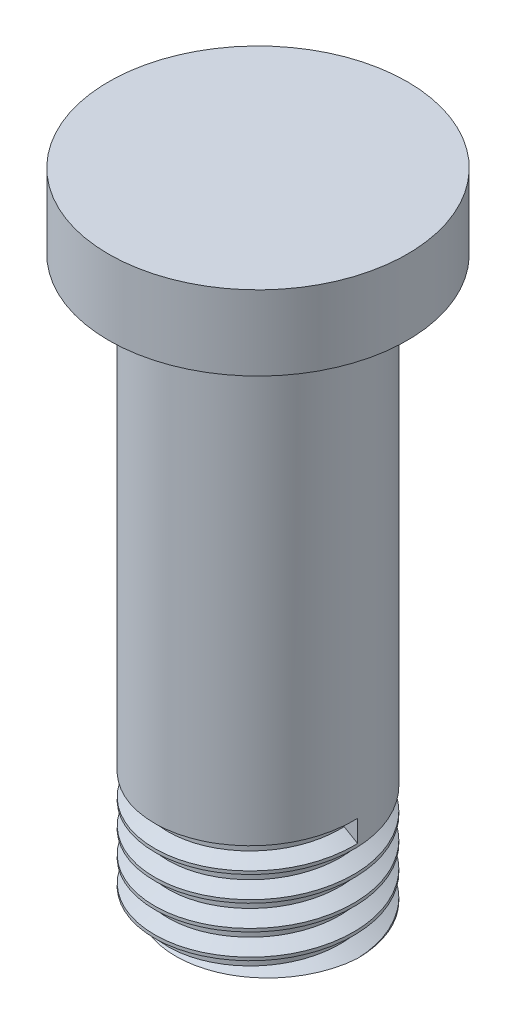
SolidWorks part; units mm, degrees
ref_plane "Front Plane" through (0, 0, 0) normal (0, 0, 1) x (1, 0, 0)
ref_plane "Top Plane" through (0, 0, 0) normal (0, 1, 0) x (1, 0, 0)
ref_plane "Right Plane" through (0, 0, 0) normal (1, 0, 0) x (0, 0, -1)
sketch "Sketch2" plane through (0, 0, 0) normal (0, 1, 0) x (1, 0, 0)
  circle A0 centre (0, 0) radius 4
  dimension "D1" = 8
extrude "Boss-Extrude1" add sketch "Sketch2" along normal blind 18.5
sketch "Sketch3" plane through (0, 18.5, 0) normal (0, 1, 0) x (1, 0, 0)
  circle A0 centre (0, 0) radius 6
  dimension "D1" = 12
extrude "Boss-Extrude2" add sketch "Sketch3" along normal blind 3
sketch "Sketch5" plane through (0, 0, 0) normal (0, -1, 0) x (1, 0, 0)
  circle A0 centre (0, 0) radius 4
extrude "Boss-Extrude3" add sketch "Sketch5" along normal blind 4
thread "Thread1" pitch 1 method cut profile "Thread Profile1" start angle 0, offset 1, length 5, pitch 1, diameter 8
ref_plane "Plane1" through (4, -5, 0) normal (0, 0, 1) x (1, 0, 0)
sketch "Thread Profile1" plane through (4, -5, 0) normal (0, 0, 1) x (1, 0, 0)
  line L0 (0, 0) -> (0, 1) construction
  line L11 (0, 0) -> (0, 0.875)
  line L12 (0, 0.875) -> (-0.5413, 0.5625)
  line L13 (-0.5413, 0.5625) -> (-0.5413, 0.3125)
  line L15 (-0.5413, 0.3125) -> (0, 0)
  line L17 (-0.5413, 0.4375) -> (0, 0.4375) construction
  point P2 (0, 0)
  dimension "Pitch" = 1
  dimension "Profile_Angle" = 60
  dimension "Profile_Land" = 0.25
  dimension "Profile_Height" = 0.5413
